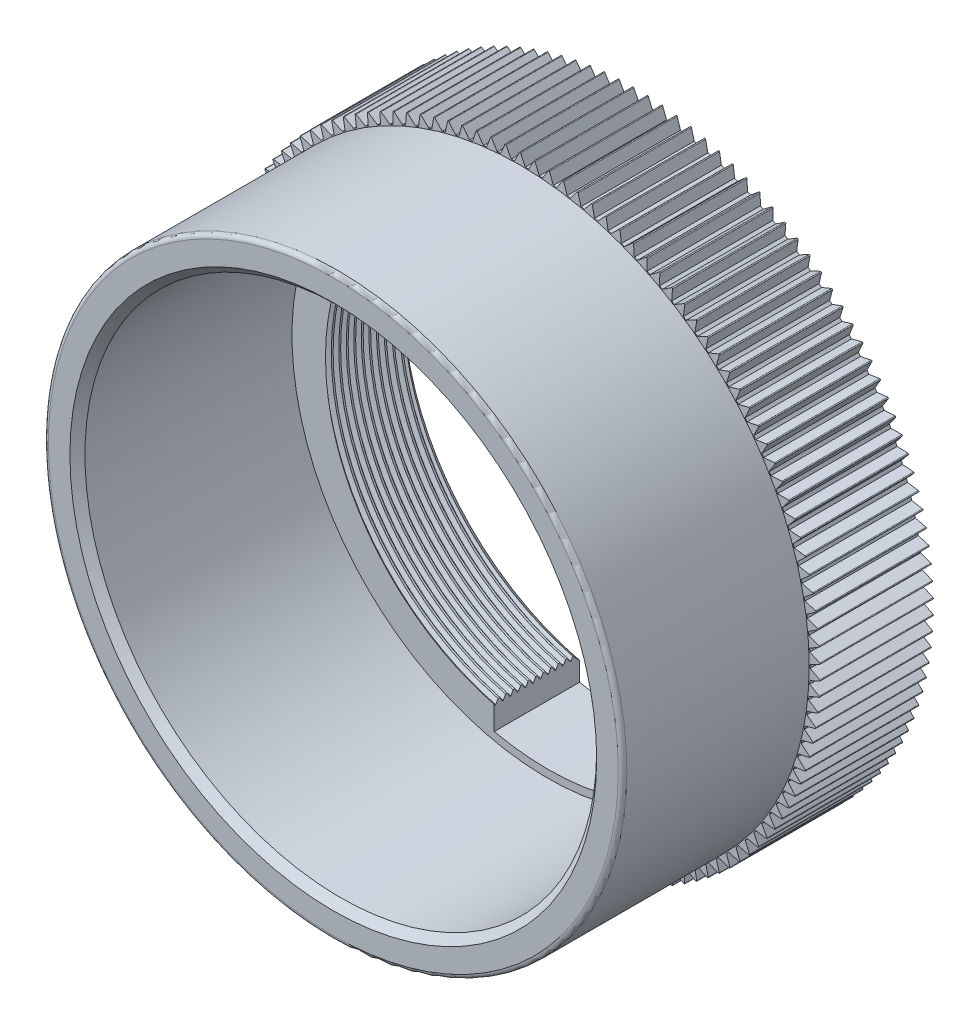
SolidWorks part; units mm, degrees
ref_plane "Plano frontal" through (0, 0, 0) normal (0, 0, 1) x (1, 0, 0)
ref_plane "Plano superior" through (0, 0, 0) normal (0, 1, 0) x (1, 0, 0)
ref_plane "Plano direito" through (0, 0, 0) normal (1, 0, 0) x (0, 0, -1)
sketch "Esboço1" plane through (0, 0, 0) normal (0, 0, 1) x (1, 0, 0)
  line L0 (0, 14) -> (0, 13.994) construction
  line L1 (0.4035, 13.5163) -> (0.6484, 13.9622)
  line L2 (-0.25, 13.52) -> (-0.027, 13.9772)
  line L3 (0.25, 13.52) -> (0.027, 13.9772)
  line L4 (0.9029, 13.4921) -> (0.7022, 13.9596)
  line L5 (1.056, 13.481) -> (1.3222, 13.9145)
  line L6 (1.5537, 13.4328) -> (1.3758, 13.9093)
  line L7 (1.7061, 13.4142) -> (1.9929, 13.8344)
  line L8 (2.2009, 13.342) -> (2.0462, 13.8266)
  line L9 (2.3522, 13.3162) -> (2.6589, 13.722)
  line L10 (2.8429, 13.2201) -> (2.7119, 13.7116)
  line L11 (2.9928, 13.187) -> (3.3188, 13.5775)
  line L12 (3.4783, 13.0673) -> (3.3711, 13.5646)
  line L13 (3.6264, 13.027) -> (3.9709, 13.4013)
  line L14 (4.1055, 12.884) -> (4.0226, 13.3859)
  line L15 (4.2516, 12.8366) -> (4.6137, 13.1938)
  line L16 (4.7232, 12.6706) -> (4.6646, 13.1759)
  line L17 (4.8668, 12.6162) -> (5.2458, 12.9555)
  line L18 (5.3299, 12.4276) -> (5.2957, 12.9352)
  line L19 (5.4706, 12.3663) -> (5.8656, 12.6869)
  line L20 (5.9241, 12.1556) -> (5.9145, 12.6642)
  line L21 (6.0617, 12.0875) -> (6.4717, 12.3887)
  line L22 (6.5044, 11.8552) -> (6.5194, 12.3637)
  line L23 (6.6386, 11.7806) -> (7.0626, 12.0616)
  line L24 (7.0696, 11.5271) -> (7.1091, 12.0342)
  line L25 (7.2, 11.4461) -> (7.6371, 11.7063)
  line L26 (7.6182, 11.1721) -> (7.6822, 11.6767)
  line L27 (7.7446, 11.0849) -> (8.1938, 11.3236)
  line L28 (8.1491, 10.791) -> (8.2374, 11.2919)
  line L29 (8.2711, 10.6977) -> (8.7313, 10.9145)
  line L30 (8.6609, 10.3847) -> (8.7733, 10.8808)
  line L31 (8.7783, 10.2856) -> (9.2484, 10.48)
  line L32 (9.1525, 9.9541) -> (9.2888, 10.4442)
  line L33 (9.265, 9.8495) -> (9.7439, 10.0209)
  line L34 (9.6228, 9.5003) -> (9.7825, 9.9832)
  line L35 (9.73, 9.3904) -> (10.2167, 9.5384)
  line L36 (10.0705, 9.0243) -> (10.2534, 9.4989)
  line L37 (10.1723, 8.9093) -> (10.6656, 9.0337)
  line L38 (10.4948, 8.5272) -> (10.7004, 8.9925)
  line L39 (10.5909, 8.4075) -> (11.0896, 8.5079)
  line L40 (10.8945, 8.0102) -> (11.1223, 8.465)
  line L41 (10.9847, 7.886) -> (11.4877, 7.9621)
  line L42 (11.2688, 7.4745) -> (11.5183, 7.9178)
  line L43 (11.3529, 7.3461) -> (11.859, 7.3978)
  line L44 (11.6167, 6.9213) -> (11.8874, 7.352)
  line L45 (11.6946, 6.789) -> (12.2025, 6.8162)
  line L46 (11.9375, 6.352) -> (12.2287, 6.7691)
  line L47 (12.0089, 6.2161) -> (12.5176, 6.2187)
  line L48 (12.2305, 5.7678) -> (12.5415, 6.1704)
  line L49 (12.2952, 5.6286) -> (12.8034, 5.6067)
  line L50 (12.4949, 5.1702) -> (12.8249, 5.5573)
  line L51 (12.5528, 5.028) -> (13.0593, 4.9816)
  line L52 (12.7301, 4.5605) -> (13.0785, 4.9312)
  line L53 (12.781, 4.4157) -> (13.2848, 4.3448)
  line L54 (12.9355, 3.9401) -> (13.3014, 4.2935)
  line L55 (12.9794, 3.793) -> (13.4792, 3.6979)
  line L56 (13.1108, 3.3106) -> (13.4933, 3.6459)
  line L57 (13.1475, 3.1615) -> (13.6421, 3.0424)
  line L58 (13.2554, 2.6733) -> (13.6537, 2.9897)
  line L59 (13.2849, 2.5226) -> (13.7731, 2.3797)
  line L60 (13.3691, 2.0298) -> (13.7822, 2.3266)
  line L61 (13.3913, 1.8778) -> (13.872, 1.7115)
  line L62 (13.4516, 1.3815) -> (13.8785, 1.658)
  line L63 (13.4664, 1.2287) -> (13.9385, 1.0393)
  line L64 (13.5026, 0.73) -> (13.9424, 0.9855)
  line L65 (13.51, 0.5766) -> (13.9725, 0.3647)
  line L66 (13.5221, 0.0768) -> (13.9738, 0.3108)
  line L67 (13.5221, -0.0768) -> (13.9738, -0.3108)
  line L68 (13.51, -0.5766) -> (13.9725, -0.3647)
  line L69 (13.5026, -0.73) -> (13.9424, -0.9855)
  line L70 (13.4664, -1.2287) -> (13.9385, -1.0393)
  line L71 (13.4516, -1.3815) -> (13.8785, -1.658)
  line L72 (13.3913, -1.8778) -> (13.872, -1.7115)
  line L73 (13.3691, -2.0298) -> (13.7822, -2.3266)
  line L74 (13.2849, -2.5226) -> (13.7731, -2.3797)
  line L75 (13.2554, -2.6733) -> (13.6537, -2.9897)
  line L76 (13.1475, -3.1615) -> (13.6421, -3.0424)
  line L77 (13.1108, -3.3106) -> (13.4933, -3.6459)
  line L78 (12.9794, -3.793) -> (13.4792, -3.6979)
  line L79 (12.9355, -3.9401) -> (13.3014, -4.2935)
  line L80 (12.781, -4.4157) -> (13.2848, -4.3448)
  line L81 (12.7301, -4.5605) -> (13.0785, -4.9312)
  line L82 (12.5528, -5.028) -> (13.0593, -4.9816)
  line L83 (12.4949, -5.1702) -> (12.8249, -5.5573)
  line L84 (12.2952, -5.6286) -> (12.8034, -5.6067)
  line L85 (12.2305, -5.7678) -> (12.5415, -6.1704)
  line L86 (12.0089, -6.2161) -> (12.5176, -6.2187)
  line L87 (11.9375, -6.352) -> (12.2287, -6.7691)
  line L88 (11.6946, -6.789) -> (12.2025, -6.8162)
  line L89 (11.6167, -6.9213) -> (11.8874, -7.352)
  line L90 (11.3529, -7.3461) -> (11.859, -7.3978)
  line L91 (11.2688, -7.4745) -> (11.5183, -7.9178)
  line L92 (10.9847, -7.886) -> (11.4877, -7.9621)
  line L93 (10.8945, -8.0102) -> (11.1223, -8.465)
  line L94 (10.5909, -8.4075) -> (11.0896, -8.5079)
  line L95 (10.4948, -8.5272) -> (10.7004, -8.9925)
  line L96 (10.1723, -8.9093) -> (10.6656, -9.0337)
  line L97 (10.0705, -9.0243) -> (10.2534, -9.4989)
  line L98 (9.73, -9.3904) -> (10.2167, -9.5384)
  line L99 (9.6228, -9.5003) -> (9.7825, -9.9832)
  line L100 (9.265, -9.8495) -> (9.7439, -10.0209)
  line L101 (9.1525, -9.9541) -> (9.2888, -10.4442)
  line L102 (8.7783, -10.2856) -> (9.2484, -10.48)
  line L103 (8.6609, -10.3847) -> (8.7733, -10.8808)
  line L104 (8.2711, -10.6977) -> (8.7313, -10.9145)
  line L105 (8.1491, -10.791) -> (8.2374, -11.2919)
  line L106 (7.7446, -11.0849) -> (8.1938, -11.3236)
  line L107 (7.6182, -11.1721) -> (7.6822, -11.6767)
  line L108 (7.2, -11.4461) -> (7.6371, -11.7063)
  line L109 (7.0696, -11.5271) -> (7.1091, -12.0342)
  line L110 (6.6386, -11.7806) -> (7.0626, -12.0616)
  line L111 (6.5044, -11.8552) -> (6.5194, -12.3637)
  line L112 (6.0617, -12.0875) -> (6.4717, -12.3887)
  line L113 (5.9241, -12.1556) -> (5.9145, -12.6642)
  line L114 (5.4706, -12.3663) -> (5.8656, -12.6869)
  line L115 (5.3299, -12.4276) -> (5.2957, -12.9352)
  line L116 (4.8668, -12.6162) -> (5.2458, -12.9555)
  line L117 (4.7232, -12.6706) -> (4.6646, -13.1759)
  line L118 (4.2516, -12.8366) -> (4.6137, -13.1938)
  line L119 (4.1055, -12.884) -> (4.0226, -13.3859)
  line L120 (3.6264, -13.027) -> (3.9709, -13.4013)
  line L121 (3.4783, -13.0673) -> (3.3711, -13.5646)
  line L122 (2.9928, -13.187) -> (3.3188, -13.5775)
  line L123 (2.8429, -13.2201) -> (2.7119, -13.7116)
  line L124 (2.3522, -13.3162) -> (2.6589, -13.722)
  line L125 (2.2009, -13.342) -> (2.0462, -13.8266)
  line L126 (1.7061, -13.4142) -> (1.9929, -13.8344)
  line L127 (1.5537, -13.4328) -> (1.3758, -13.9093)
  line L128 (1.056, -13.481) -> (1.3222, -13.9145)
  line L129 (0.9029, -13.4921) -> (0.7022, -13.9596)
  line L130 (0.4035, -13.5163) -> (0.6484, -13.9622)
  line L131 (0.25, -13.52) -> (0.027, -13.9772)
  line L132 (-0.25, -13.52) -> (-0.027, -13.9772)
  line L133 (-0.4035, -13.5163) -> (-0.6484, -13.9622)
  line L134 (-0.9029, -13.4921) -> (-0.7022, -13.9596)
  line L135 (-1.056, -13.481) -> (-1.3222, -13.9145)
  line L136 (-1.5537, -13.4328) -> (-1.3758, -13.9093)
  line L137 (-1.7061, -13.4142) -> (-1.9929, -13.8344)
  line L138 (-2.2009, -13.342) -> (-2.0462, -13.8266)
  line L139 (-2.3522, -13.3162) -> (-2.6589, -13.722)
  line L140 (-2.8429, -13.2201) -> (-2.7119, -13.7116)
  line L141 (-2.9928, -13.187) -> (-3.3188, -13.5775)
  line L142 (-3.4783, -13.0673) -> (-3.3711, -13.5646)
  line L143 (-3.6264, -13.027) -> (-3.9709, -13.4013)
  line L144 (-4.1055, -12.884) -> (-4.0226, -13.3859)
  line L145 (-4.2516, -12.8366) -> (-4.6137, -13.1938)
  line L146 (-4.7232, -12.6706) -> (-4.6646, -13.1759)
  line L147 (-4.8668, -12.6162) -> (-5.2458, -12.9555)
  line L148 (-5.3299, -12.4276) -> (-5.2957, -12.9352)
  line L149 (-5.4706, -12.3663) -> (-5.8656, -12.6869)
  line L150 (-5.9241, -12.1556) -> (-5.9145, -12.6642)
  line L151 (-6.0617, -12.0875) -> (-6.4717, -12.3887)
  line L152 (-6.5044, -11.8552) -> (-6.5194, -12.3637)
  line L153 (-6.6386, -11.7806) -> (-7.0626, -12.0616)
  line L154 (-7.0696, -11.5271) -> (-7.1091, -12.0342)
  line L155 (-7.2, -11.4461) -> (-7.6371, -11.7063)
  line L156 (-7.6182, -11.1721) -> (-7.6822, -11.6767)
  line L157 (-7.7446, -11.0849) -> (-8.1938, -11.3236)
  line L158 (-8.1491, -10.791) -> (-8.2374, -11.2919)
  line L159 (-8.2711, -10.6977) -> (-8.7313, -10.9145)
  line L160 (-8.6609, -10.3847) -> (-8.7733, -10.8808)
  line L161 (-8.7783, -10.2856) -> (-9.2484, -10.48)
  line L162 (-9.1525, -9.9541) -> (-9.2888, -10.4442)
  line L163 (-9.265, -9.8495) -> (-9.7439, -10.0209)
  line L164 (-9.6228, -9.5003) -> (-9.7825, -9.9832)
  line L165 (-9.73, -9.3904) -> (-10.2167, -9.5384)
  line L166 (-10.0705, -9.0243) -> (-10.2534, -9.4989)
  line L167 (-10.1723, -8.9093) -> (-10.6656, -9.0337)
  line L168 (-10.4948, -8.5272) -> (-10.7004, -8.9925)
  line L169 (-10.5909, -8.4075) -> (-11.0896, -8.5079)
  line L170 (-10.8945, -8.0102) -> (-11.1223, -8.465)
  line L171 (-10.9847, -7.886) -> (-11.4877, -7.9621)
  line L172 (-11.2688, -7.4745) -> (-11.5183, -7.9178)
  line L173 (-11.3529, -7.3461) -> (-11.859, -7.3978)
  line L174 (-11.6167, -6.9213) -> (-11.8874, -7.352)
  line L175 (-11.6946, -6.789) -> (-12.2025, -6.8162)
  line L176 (-11.9375, -6.352) -> (-12.2287, -6.7691)
  line L177 (-12.0089, -6.2161) -> (-12.5176, -6.2187)
  line L178 (-12.2305, -5.7678) -> (-12.5415, -6.1704)
  line L179 (-12.2952, -5.6286) -> (-12.8034, -5.6067)
  line L180 (-12.4949, -5.1702) -> (-12.8249, -5.5573)
  line L181 (-12.5528, -5.028) -> (-13.0593, -4.9816)
  line L182 (-12.7301, -4.5605) -> (-13.0785, -4.9312)
  line L183 (-12.781, -4.4157) -> (-13.2848, -4.3448)
  line L184 (-12.9355, -3.9401) -> (-13.3014, -4.2935)
  line L185 (-12.9794, -3.793) -> (-13.4792, -3.6979)
  line L186 (-13.1108, -3.3106) -> (-13.4933, -3.6459)
  line L187 (-13.1475, -3.1615) -> (-13.6421, -3.0424)
  line L188 (-13.2554, -2.6733) -> (-13.6537, -2.9897)
  line L189 (-13.2849, -2.5226) -> (-13.7731, -2.3797)
  line L190 (-13.3691, -2.0298) -> (-13.7822, -2.3266)
  line L191 (-13.3913, -1.8778) -> (-13.872, -1.7115)
  line L192 (-13.4516, -1.3815) -> (-13.8785, -1.658)
  line L193 (-13.4664, -1.2287) -> (-13.9385, -1.0393)
  line L194 (-13.5026, -0.73) -> (-13.9424, -0.9855)
  line L195 (-13.51, -0.5766) -> (-13.9725, -0.3647)
  line L196 (-13.5221, -0.0768) -> (-13.9738, -0.3108)
  line L197 (-13.5221, 0.0768) -> (-13.9738, 0.3108)
  line L198 (-13.51, 0.5766) -> (-13.9725, 0.3647)
  line L199 (-13.5026, 0.73) -> (-13.9424, 0.9855)
  line L200 (-13.4664, 1.2287) -> (-13.9385, 1.0393)
  line L201 (-13.4516, 1.3815) -> (-13.8785, 1.658)
  line L202 (-13.3913, 1.8778) -> (-13.872, 1.7115)
  line L203 (-13.3691, 2.0298) -> (-13.7822, 2.3266)
  line L204 (-13.2849, 2.5226) -> (-13.7731, 2.3797)
  line L205 (-13.2554, 2.6733) -> (-13.6537, 2.9897)
  line L206 (-13.1475, 3.1615) -> (-13.6421, 3.0424)
  line L207 (-13.1108, 3.3106) -> (-13.4933, 3.6459)
  line L208 (-12.9794, 3.793) -> (-13.4792, 3.6979)
  line L209 (-12.9355, 3.9401) -> (-13.3014, 4.2935)
  line L210 (-12.781, 4.4157) -> (-13.2848, 4.3448)
  line L211 (-12.7301, 4.5605) -> (-13.0785, 4.9312)
  line L212 (-12.5528, 5.028) -> (-13.0593, 4.9816)
  line L213 (-12.4949, 5.1702) -> (-12.8249, 5.5573)
  line L214 (-12.2952, 5.6286) -> (-12.8034, 5.6067)
  line L215 (-12.2305, 5.7678) -> (-12.5415, 6.1704)
  line L216 (-12.0089, 6.2161) -> (-12.5176, 6.2187)
  line L217 (-11.9375, 6.352) -> (-12.2287, 6.7691)
  line L218 (-11.6946, 6.789) -> (-12.2025, 6.8162)
  line L219 (-11.6167, 6.9213) -> (-11.8874, 7.352)
  line L220 (-11.3529, 7.3461) -> (-11.859, 7.3978)
  line L221 (-11.2688, 7.4745) -> (-11.5183, 7.9178)
  line L222 (-10.9847, 7.886) -> (-11.4877, 7.9621)
  line L223 (-10.8945, 8.0102) -> (-11.1223, 8.465)
  line L224 (-10.5909, 8.4075) -> (-11.0896, 8.5079)
  line L225 (-10.4948, 8.5272) -> (-10.7004, 8.9925)
  line L226 (-10.1723, 8.9093) -> (-10.6656, 9.0337)
  line L227 (-10.0705, 9.0243) -> (-10.2534, 9.4989)
  line L228 (-9.73, 9.3904) -> (-10.2167, 9.5384)
  line L229 (-9.6228, 9.5003) -> (-9.7825, 9.9832)
  line L230 (-9.265, 9.8495) -> (-9.7439, 10.0209)
  line L231 (-9.1525, 9.9541) -> (-9.2888, 10.4442)
  line L232 (-8.7783, 10.2856) -> (-9.2484, 10.48)
  line L233 (-8.6609, 10.3847) -> (-8.7733, 10.8808)
  line L234 (-8.2711, 10.6977) -> (-8.7313, 10.9145)
  line L235 (-8.1491, 10.791) -> (-8.2374, 11.2919)
  line L236 (-7.7446, 11.0849) -> (-8.1938, 11.3236)
  line L237 (-7.6182, 11.1721) -> (-7.6822, 11.6767)
  line L238 (-7.2, 11.4461) -> (-7.6371, 11.7063)
  line L239 (-7.0696, 11.5271) -> (-7.1091, 12.0342)
  line L240 (-6.6386, 11.7806) -> (-7.0626, 12.0616)
  line L241 (-6.5044, 11.8552) -> (-6.5194, 12.3637)
  line L242 (-6.0617, 12.0875) -> (-6.4717, 12.3887)
  line L243 (-5.9241, 12.1556) -> (-5.9145, 12.6642)
  line L244 (-5.4706, 12.3663) -> (-5.8656, 12.6869)
  line L245 (-5.3299, 12.4276) -> (-5.2957, 12.9352)
  line L246 (-4.8668, 12.6162) -> (-5.2458, 12.9555)
  line L247 (-4.7232, 12.6706) -> (-4.6646, 13.1759)
  line L248 (-4.2516, 12.8366) -> (-4.6137, 13.1938)
  line L249 (-4.1055, 12.884) -> (-4.0226, 13.3859)
  line L250 (-3.6264, 13.027) -> (-3.9709, 13.4013)
  line L251 (-3.4783, 13.0673) -> (-3.3711, 13.5646)
  line L252 (-2.9928, 13.187) -> (-3.3188, 13.5775)
  line L253 (-2.8429, 13.2201) -> (-2.7119, 13.7116)
  line L254 (-2.3522, 13.3162) -> (-2.6589, 13.722)
  line L255 (-2.2009, 13.342) -> (-2.0462, 13.8266)
  line L256 (-1.7061, 13.4142) -> (-1.9929, 13.8344)
  line L257 (-1.5537, 13.4328) -> (-1.3758, 13.9093)
  line L258 (-1.056, 13.481) -> (-1.3222, 13.9145)
  line L259 (-0.9029, 13.4921) -> (-0.7022, 13.9596)
  line L260 (-0.4035, 13.5163) -> (-0.6484, 13.9622)
  line L261 (0.25, 13.52) -> (0.4035, 13.5163)
  line L262 (0.9029, 13.4921) -> (1.056, 13.481)
  line L263 (1.5537, 13.4328) -> (1.7061, 13.4142)
  line L264 (2.2009, 13.342) -> (2.3522, 13.3162)
  line L265 (2.8429, 13.2201) -> (2.9928, 13.187)
  line L266 (3.4783, 13.0673) -> (3.6264, 13.027)
  line L267 (4.1055, 12.884) -> (4.2516, 12.8366)
  line L268 (4.7232, 12.6706) -> (4.8668, 12.6162)
  line L269 (5.3299, 12.4276) -> (5.4706, 12.3663)
  line L270 (5.9241, 12.1556) -> (6.0617, 12.0875)
  line L271 (6.5044, 11.8552) -> (6.6386, 11.7806)
  line L272 (7.0696, 11.5271) -> (7.2, 11.4461)
  line L273 (7.6182, 11.1721) -> (7.7446, 11.0849)
  line L274 (8.1491, 10.791) -> (8.2711, 10.6977)
  line L275 (8.6609, 10.3847) -> (8.7783, 10.2856)
  line L276 (9.1525, 9.9541) -> (9.265, 9.8495)
  line L277 (9.6228, 9.5003) -> (9.73, 9.3904)
  line L278 (10.0705, 9.0243) -> (10.1723, 8.9093)
  line L279 (10.4948, 8.5272) -> (10.5909, 8.4075)
  line L280 (10.8945, 8.0102) -> (10.9847, 7.886)
  line L281 (11.2688, 7.4745) -> (11.3529, 7.3461)
  line L282 (11.6167, 6.9213) -> (11.6946, 6.789)
  line L283 (11.9375, 6.352) -> (12.0089, 6.2161)
  line L284 (12.2305, 5.7678) -> (12.2952, 5.6286)
  line L285 (12.4949, 5.1702) -> (12.5528, 5.028)
  line L286 (12.7301, 4.5605) -> (12.781, 4.4157)
  line L287 (12.9355, 3.9401) -> (12.9794, 3.793)
  line L288 (13.1108, 3.3106) -> (13.1475, 3.1615)
  line L289 (13.2554, 2.6733) -> (13.2849, 2.5226)
  line L290 (13.3691, 2.0298) -> (13.3913, 1.8778)
  line L291 (13.4516, 1.3815) -> (13.4664, 1.2287)
  line L292 (13.5026, 0.73) -> (13.51, 0.5766)
  line L293 (13.5221, 0.0768) -> (13.5221, -0.0768)
  line L294 (13.51, -0.5766) -> (13.5026, -0.73)
  line L295 (13.4664, -1.2287) -> (13.4516, -1.3815)
  line L296 (13.3913, -1.8778) -> (13.3691, -2.0298)
  line L297 (13.2849, -2.5226) -> (13.2554, -2.6733)
  line L298 (13.1475, -3.1615) -> (13.1108, -3.3106)
  line L299 (12.9794, -3.793) -> (12.9355, -3.9401)
  line L300 (12.781, -4.4157) -> (12.7301, -4.5605)
  line L301 (12.5528, -5.028) -> (12.4949, -5.1702)
  line L302 (12.2952, -5.6286) -> (12.2305, -5.7678)
  line L303 (12.0089, -6.2161) -> (11.9375, -6.352)
  line L304 (11.6946, -6.789) -> (11.6167, -6.9213)
  line L305 (11.3529, -7.3461) -> (11.2688, -7.4745)
  line L306 (10.9847, -7.886) -> (10.8945, -8.0102)
  line L307 (10.5909, -8.4075) -> (10.4948, -8.5272)
  line L308 (10.1723, -8.9093) -> (10.0705, -9.0243)
  line L309 (9.73, -9.3904) -> (9.6228, -9.5003)
  line L310 (9.265, -9.8495) -> (9.1525, -9.9541)
  line L311 (8.7783, -10.2856) -> (8.6609, -10.3847)
  line L312 (8.2711, -10.6977) -> (8.1491, -10.791)
  line L313 (7.7446, -11.0849) -> (7.6182, -11.1721)
  line L314 (7.2, -11.4461) -> (7.0696, -11.5271)
  line L315 (6.6386, -11.7806) -> (6.5044, -11.8552)
  line L316 (6.0617, -12.0875) -> (5.9241, -12.1556)
  line L317 (5.4706, -12.3663) -> (5.3299, -12.4276)
  line L318 (4.8668, -12.6162) -> (4.7232, -12.6706)
  line L319 (4.2516, -12.8366) -> (4.1055, -12.884)
  line L320 (3.6264, -13.027) -> (3.4783, -13.0673)
  line L321 (2.9928, -13.187) -> (2.8429, -13.2201)
  line L322 (2.3522, -13.3162) -> (2.2009, -13.342)
  line L323 (1.7061, -13.4142) -> (1.5537, -13.4328)
  line L324 (1.056, -13.481) -> (0.9029, -13.4921)
  line L325 (0.4035, -13.5163) -> (0.25, -13.52)
  line L326 (-0.25, -13.52) -> (-0.4035, -13.5163)
  line L327 (-0.9029, -13.4921) -> (-1.056, -13.481)
  line L328 (-1.5537, -13.4328) -> (-1.7061, -13.4142)
  line L329 (-2.2009, -13.342) -> (-2.3522, -13.3162)
  line L330 (-2.8429, -13.2201) -> (-2.9928, -13.187)
  line L331 (-3.4783, -13.0673) -> (-3.6264, -13.027)
  line L332 (-4.1055, -12.884) -> (-4.2516, -12.8366)
  line L333 (-4.7232, -12.6706) -> (-4.8668, -12.6162)
  line L334 (-5.3299, -12.4276) -> (-5.4706, -12.3663)
  line L335 (-5.9241, -12.1556) -> (-6.0617, -12.0875)
  line L336 (-6.5044, -11.8552) -> (-6.6386, -11.7806)
  line L337 (-7.0696, -11.5271) -> (-7.2, -11.4461)
  line L338 (-7.6182, -11.1721) -> (-7.7446, -11.0849)
  line L339 (-8.1491, -10.791) -> (-8.2711, -10.6977)
  line L340 (-8.6609, -10.3847) -> (-8.7783, -10.2856)
  line L341 (-9.1525, -9.9541) -> (-9.265, -9.8495)
  line L342 (-9.6228, -9.5003) -> (-9.73, -9.3904)
  line L343 (-10.0705, -9.0243) -> (-10.1723, -8.9093)
  line L344 (-10.4948, -8.5272) -> (-10.5909, -8.4075)
  line L345 (-10.8945, -8.0102) -> (-10.9847, -7.886)
  line L346 (-11.2688, -7.4745) -> (-11.3529, -7.3461)
  line L347 (-11.6167, -6.9213) -> (-11.6946, -6.789)
  line L348 (-11.9375, -6.352) -> (-12.0089, -6.2161)
  line L349 (-12.2305, -5.7678) -> (-12.2952, -5.6286)
  line L350 (-12.4949, -5.1702) -> (-12.5528, -5.028)
  line L351 (-12.7301, -4.5605) -> (-12.781, -4.4157)
  line L352 (-12.9355, -3.9401) -> (-12.9794, -3.793)
  line L353 (-13.1108, -3.3106) -> (-13.1475, -3.1615)
  line L354 (-13.2554, -2.6733) -> (-13.2849, -2.5226)
  line L355 (-13.3691, -2.0298) -> (-13.3913, -1.8778)
  line L356 (-13.4516, -1.3815) -> (-13.4664, -1.2287)
  line L357 (-13.5026, -0.73) -> (-13.51, -0.5766)
  line L358 (-13.5221, -0.0768) -> (-13.5221, 0.0768)
  line L359 (-13.51, 0.5766) -> (-13.5026, 0.73)
  line L360 (-13.4664, 1.2287) -> (-13.4516, 1.3815)
  line L361 (-13.3913, 1.8778) -> (-13.3691, 2.0298)
  line L362 (-13.2849, 2.5226) -> (-13.2554, 2.6733)
  line L363 (-13.1475, 3.1615) -> (-13.1108, 3.3106)
  line L364 (-12.9794, 3.793) -> (-12.9355, 3.9401)
  line L365 (-12.781, 4.4157) -> (-12.7301, 4.5605)
  line L366 (-12.5528, 5.028) -> (-12.4949, 5.1702)
  line L367 (-12.2952, 5.6286) -> (-12.2305, 5.7678)
  line L368 (-12.0089, 6.2161) -> (-11.9375, 6.352)
  line L369 (-11.6946, 6.789) -> (-11.6167, 6.9213)
  line L370 (-11.3529, 7.3461) -> (-11.2688, 7.4745)
  line L371 (-10.9847, 7.886) -> (-10.8945, 8.0102)
  line L372 (-10.5909, 8.4075) -> (-10.4948, 8.5272)
  line L373 (-10.1723, 8.9093) -> (-10.0705, 9.0243)
  line L374 (-9.73, 9.3904) -> (-9.6228, 9.5003)
  line L375 (-9.265, 9.8495) -> (-9.1525, 9.9541)
  line L376 (-8.7783, 10.2856) -> (-8.6609, 10.3847)
  line L377 (-8.2711, 10.6977) -> (-8.1491, 10.791)
  line L378 (-7.7446, 11.0849) -> (-7.6182, 11.1721)
  line L379 (-7.2, 11.4461) -> (-7.0696, 11.5271)
  line L380 (-6.6386, 11.7806) -> (-6.5044, 11.8552)
  line L381 (-6.0617, 12.0875) -> (-5.9241, 12.1556)
  line L382 (-5.4706, 12.3663) -> (-5.3299, 12.4276)
  line L383 (-4.8668, 12.6162) -> (-4.7232, 12.6706)
  line L384 (-4.2516, 12.8366) -> (-4.1055, 12.884)
  line L385 (-3.6264, 13.027) -> (-3.4783, 13.0673)
  line L386 (-2.9928, 13.187) -> (-2.8429, 13.2201)
  line L387 (-2.3522, 13.3162) -> (-2.2009, 13.342)
  line L388 (-1.7061, 13.4142) -> (-1.5537, 13.4328)
  line L389 (-1.056, 13.481) -> (-0.9029, 13.4921)
  line L390 (-0.4035, 13.5163) -> (-0.25, 13.52)
  arc A0 (0.7022, 13.9596) -> (0.6484, 13.9622) centre (0.6746, 13.9477) ccw
  arc A1 (0.027, 13.9772) -> (-0.027, 13.9772) centre (0, 13.964) ccw
  arc A2 (1.3758, 13.9093) -> (1.3222, 13.9145) centre (1.3477, 13.8989) ccw
  arc A3 (2.0462, 13.8266) -> (1.9929, 13.8344) centre (2.0177, 13.8175) ccw
  arc A4 (2.7119, 13.7116) -> (2.6589, 13.722) centre (2.6829, 13.7039) ccw
  arc A5 (3.3711, 13.5646) -> (3.3188, 13.5775) centre (3.3418, 13.5583) ccw
  arc A6 (4.0226, 13.3859) -> (3.9709, 13.4013) centre (3.993, 13.381) ccw
  arc A7 (4.6646, 13.1759) -> (4.6137, 13.1938) centre (4.6348, 13.1724) ccw
  arc A8 (5.2957, 12.9352) -> (5.2458, 12.9555) centre (5.2658, 12.9331) ccw
  arc A9 (5.9145, 12.6642) -> (5.8656, 12.6869) centre (5.8845, 12.6636) ccw
  arc A10 (6.5194, 12.3637) -> (6.4717, 12.3887) centre (6.4894, 12.3645) ccw
  arc A11 (7.1091, 12.0342) -> (7.0626, 12.0616) centre (7.0792, 12.0366) ccw
  arc A12 (7.6822, 11.6767) -> (7.6371, 11.7063) centre (7.6525, 11.6805) ccw
  arc A13 (8.2374, 11.2919) -> (8.1938, 11.3236) centre (8.2079, 11.2971) ccw
  arc A14 (8.7733, 10.8808) -> (8.7313, 10.9145) centre (8.7441, 10.8874) ccw
  arc A15 (9.2888, 10.4442) -> (9.2484, 10.48) centre (9.2599, 10.4522) ccw
  arc A16 (9.7825, 9.9832) -> (9.7439, 10.0209) centre (9.754, 9.9927) ccw
  arc A17 (10.2534, 9.4989) -> (10.2167, 9.5384) centre (10.2254, 9.5097) ccw
  arc A18 (10.7004, 8.9925) -> (10.6656, 9.0337) centre (10.6729, 9.0046) ccw
  arc A19 (11.1223, 8.465) -> (11.0896, 8.5079) centre (11.0955, 8.4784) ccw
  arc A20 (11.5183, 7.9178) -> (11.4877, 7.9621) centre (11.4922, 7.9325) ccw
  arc A21 (11.8874, 7.352) -> (11.859, 7.3978) centre (11.862, 7.368) ccw
  arc A22 (12.2287, 6.7691) -> (12.2025, 6.8162) centre (12.2041, 6.7863) ccw
  arc A23 (12.5415, 6.1704) -> (12.5176, 6.2187) centre (12.5177, 6.1887) ccw
  arc A24 (12.8249, 5.5573) -> (12.8034, 5.6067) centre (12.8021, 5.5767) ccw
  arc A25 (13.0785, 4.9312) -> (13.0593, 4.9816) centre (13.0566, 4.9517) ccw
  arc A26 (13.3014, 4.2935) -> (13.2848, 4.3448) centre (13.2806, 4.3151) ccw
  arc A27 (13.4933, 3.6459) -> (13.4792, 3.6979) centre (13.4736, 3.6685) ccw
  arc A28 (13.6537, 2.9897) -> (13.6421, 3.0424) centre (13.6351, 3.0132) ccw
  arc A29 (13.7822, 2.3266) -> (13.7731, 2.3797) centre (13.7647, 2.3509) ccw
  arc A30 (13.8785, 1.658) -> (13.872, 1.7115) centre (13.8622, 1.6832) ccw
  arc A31 (13.9424, 0.9855) -> (13.9385, 1.0393) centre (13.9274, 1.0115) ccw
  arc A32 (13.9738, 0.3108) -> (13.9725, 0.3647) centre (13.96, 0.3374) ccw
  arc A33 (13.9725, -0.3647) -> (13.9738, -0.3108) centre (13.96, -0.3374) ccw
  arc A34 (13.9385, -1.0393) -> (13.9424, -0.9855) centre (13.9274, -1.0115) ccw
  arc A35 (13.872, -1.7115) -> (13.8785, -1.658) centre (13.8622, -1.6832) ccw
  arc A36 (13.7731, -2.3797) -> (13.7822, -2.3266) centre (13.7647, -2.3509) ccw
  arc A37 (13.6421, -3.0424) -> (13.6537, -2.9897) centre (13.6351, -3.0132) ccw
  arc A38 (13.4792, -3.6979) -> (13.4933, -3.6459) centre (13.4736, -3.6685) ccw
  arc A39 (13.2848, -4.3448) -> (13.3014, -4.2935) centre (13.2806, -4.3151) ccw
  arc A40 (13.0593, -4.9816) -> (13.0785, -4.9312) centre (13.0566, -4.9517) ccw
  arc A41 (12.8034, -5.6067) -> (12.8249, -5.5573) centre (12.8021, -5.5767) ccw
  arc A42 (12.5176, -6.2187) -> (12.5415, -6.1704) centre (12.5177, -6.1887) ccw
  arc A43 (12.2025, -6.8162) -> (12.2287, -6.7691) centre (12.2041, -6.7863) ccw
  arc A44 (11.859, -7.3978) -> (11.8874, -7.352) centre (11.862, -7.368) ccw
  arc A45 (11.4877, -7.9621) -> (11.5183, -7.9178) centre (11.4922, -7.9325) ccw
  arc A46 (11.0896, -8.5079) -> (11.1223, -8.465) centre (11.0955, -8.4784) ccw
  arc A47 (10.6656, -9.0337) -> (10.7004, -8.9925) centre (10.6729, -9.0046) ccw
  arc A48 (10.2167, -9.5384) -> (10.2534, -9.4989) centre (10.2254, -9.5097) ccw
  arc A49 (9.7439, -10.0209) -> (9.7825, -9.9832) centre (9.754, -9.9927) ccw
  arc A50 (9.2484, -10.48) -> (9.2888, -10.4442) centre (9.2599, -10.4522) ccw
  arc A51 (8.7313, -10.9145) -> (8.7733, -10.8808) centre (8.7441, -10.8874) ccw
  arc A52 (8.1938, -11.3236) -> (8.2374, -11.2919) centre (8.2079, -11.2971) ccw
  arc A53 (7.6371, -11.7063) -> (7.6822, -11.6767) centre (7.6525, -11.6805) ccw
  arc A54 (7.0626, -12.0616) -> (7.1091, -12.0342) centre (7.0792, -12.0366) ccw
  arc A55 (6.4717, -12.3887) -> (6.5194, -12.3637) centre (6.4894, -12.3645) ccw
  arc A56 (5.8656, -12.6869) -> (5.9145, -12.6642) centre (5.8845, -12.6636) ccw
  arc A57 (5.2458, -12.9555) -> (5.2957, -12.9352) centre (5.2658, -12.9331) ccw
  arc A58 (4.6137, -13.1938) -> (4.6646, -13.1759) centre (4.6348, -13.1724) ccw
  arc A59 (3.9709, -13.4013) -> (4.0226, -13.3859) centre (3.993, -13.381) ccw
  arc A60 (3.3188, -13.5775) -> (3.3711, -13.5646) centre (3.3418, -13.5583) ccw
  arc A61 (2.6589, -13.722) -> (2.7119, -13.7116) centre (2.6829, -13.7039) ccw
  arc A62 (1.9929, -13.8344) -> (2.0462, -13.8266) centre (2.0177, -13.8175) ccw
  arc A63 (1.3222, -13.9145) -> (1.3758, -13.9093) centre (1.3477, -13.8989) ccw
  arc A64 (0.6484, -13.9622) -> (0.7022, -13.9596) centre (0.6746, -13.9477) ccw
  arc A65 (-0.027, -13.9772) -> (0.027, -13.9772) centre (0, -13.964) ccw
  arc A66 (-0.7022, -13.9596) -> (-0.6484, -13.9622) centre (-0.6746, -13.9477) ccw
  arc A67 (-1.3758, -13.9093) -> (-1.3222, -13.9145) centre (-1.3477, -13.8989) ccw
  arc A68 (-2.0462, -13.8266) -> (-1.9929, -13.8344) centre (-2.0177, -13.8175) ccw
  arc A69 (-2.7119, -13.7116) -> (-2.6589, -13.722) centre (-2.6829, -13.7039) ccw
  arc A70 (-3.3711, -13.5646) -> (-3.3188, -13.5775) centre (-3.3418, -13.5583) ccw
  arc A71 (-4.0226, -13.3859) -> (-3.9709, -13.4013) centre (-3.993, -13.381) ccw
  arc A72 (-4.6646, -13.1759) -> (-4.6137, -13.1938) centre (-4.6348, -13.1724) ccw
  arc A73 (-5.2957, -12.9352) -> (-5.2458, -12.9555) centre (-5.2658, -12.9331) ccw
  arc A74 (-5.9145, -12.6642) -> (-5.8656, -12.6869) centre (-5.8845, -12.6636) ccw
  arc A75 (-6.5194, -12.3637) -> (-6.4717, -12.3887) centre (-6.4894, -12.3645) ccw
  arc A76 (-7.1091, -12.0342) -> (-7.0626, -12.0616) centre (-7.0792, -12.0366) ccw
  arc A77 (-7.6822, -11.6767) -> (-7.6371, -11.7063) centre (-7.6525, -11.6805) ccw
  arc A78 (-8.2374, -11.2919) -> (-8.1938, -11.3236) centre (-8.2079, -11.2971) ccw
  arc A79 (-8.7733, -10.8808) -> (-8.7313, -10.9145) centre (-8.7441, -10.8874) ccw
  arc A80 (-9.2888, -10.4442) -> (-9.2484, -10.48) centre (-9.2599, -10.4522) ccw
  arc A81 (-9.7825, -9.9832) -> (-9.7439, -10.0209) centre (-9.754, -9.9927) ccw
  arc A82 (-10.2534, -9.4989) -> (-10.2167, -9.5384) centre (-10.2254, -9.5097) ccw
  arc A83 (-10.7004, -8.9925) -> (-10.6656, -9.0337) centre (-10.6729, -9.0046) ccw
  arc A84 (-11.1223, -8.465) -> (-11.0896, -8.5079) centre (-11.0955, -8.4784) ccw
  arc A85 (-11.5183, -7.9178) -> (-11.4877, -7.9621) centre (-11.4922, -7.9325) ccw
  arc A86 (-11.8874, -7.352) -> (-11.859, -7.3978) centre (-11.862, -7.368) ccw
  arc A87 (-12.2287, -6.7691) -> (-12.2025, -6.8162) centre (-12.2041, -6.7863) ccw
  arc A88 (-12.5415, -6.1704) -> (-12.5176, -6.2187) centre (-12.5177, -6.1887) ccw
  arc A89 (-12.8249, -5.5573) -> (-12.8034, -5.6067) centre (-12.8021, -5.5767) ccw
  arc A90 (-13.0785, -4.9312) -> (-13.0593, -4.9816) centre (-13.0566, -4.9517) ccw
  arc A91 (-13.3014, -4.2935) -> (-13.2848, -4.3448) centre (-13.2806, -4.3151) ccw
  arc A92 (-13.4933, -3.6459) -> (-13.4792, -3.6979) centre (-13.4736, -3.6685) ccw
  arc A93 (-13.6537, -2.9897) -> (-13.6421, -3.0424) centre (-13.6351, -3.0132) ccw
  arc A94 (-13.7822, -2.3266) -> (-13.7731, -2.3797) centre (-13.7647, -2.3509) ccw
  arc A95 (-13.8785, -1.658) -> (-13.872, -1.7115) centre (-13.8622, -1.6832) ccw
  arc A96 (-13.9424, -0.9855) -> (-13.9385, -1.0393) centre (-13.9274, -1.0115) ccw
  arc A97 (-13.9738, -0.3108) -> (-13.9725, -0.3647) centre (-13.96, -0.3374) ccw
  arc A98 (-13.9725, 0.3647) -> (-13.9738, 0.3108) centre (-13.96, 0.3374) ccw
  arc A99 (-13.9385, 1.0393) -> (-13.9424, 0.9855) centre (-13.9274, 1.0115) ccw
  arc A100 (-13.872, 1.7115) -> (-13.8785, 1.658) centre (-13.8622, 1.6832) ccw
  arc A101 (-13.7731, 2.3797) -> (-13.7822, 2.3266) centre (-13.7647, 2.3509) ccw
  arc A102 (-13.6421, 3.0424) -> (-13.6537, 2.9897) centre (-13.6351, 3.0132) ccw
  arc A103 (-13.4792, 3.6979) -> (-13.4933, 3.6459) centre (-13.4736, 3.6685) ccw
  arc A104 (-13.2848, 4.3448) -> (-13.3014, 4.2935) centre (-13.2806, 4.3151) ccw
  arc A105 (-13.0593, 4.9816) -> (-13.0785, 4.9312) centre (-13.0566, 4.9517) ccw
  arc A106 (-12.8034, 5.6067) -> (-12.8249, 5.5573) centre (-12.8021, 5.5767) ccw
  arc A107 (-12.5176, 6.2187) -> (-12.5415, 6.1704) centre (-12.5177, 6.1887) ccw
  arc A108 (-12.2025, 6.8162) -> (-12.2287, 6.7691) centre (-12.2041, 6.7863) ccw
  arc A109 (-11.859, 7.3978) -> (-11.8874, 7.352) centre (-11.862, 7.368) ccw
  arc A110 (-11.4877, 7.9621) -> (-11.5183, 7.9178) centre (-11.4922, 7.9325) ccw
  arc A111 (-11.0896, 8.5079) -> (-11.1223, 8.465) centre (-11.0955, 8.4784) ccw
  arc A112 (-10.6656, 9.0337) -> (-10.7004, 8.9925) centre (-10.6729, 9.0046) ccw
  arc A113 (-10.2167, 9.5384) -> (-10.2534, 9.4989) centre (-10.2254, 9.5097) ccw
  arc A114 (-9.7439, 10.0209) -> (-9.7825, 9.9832) centre (-9.754, 9.9927) ccw
  arc A115 (-9.2484, 10.48) -> (-9.2888, 10.4442) centre (-9.2599, 10.4522) ccw
  arc A116 (-8.7313, 10.9145) -> (-8.7733, 10.8808) centre (-8.7441, 10.8874) ccw
  arc A117 (-8.1938, 11.3236) -> (-8.2374, 11.2919) centre (-8.2079, 11.2971) ccw
  arc A118 (-7.6371, 11.7063) -> (-7.6822, 11.6767) centre (-7.6525, 11.6805) ccw
  arc A119 (-7.0626, 12.0616) -> (-7.1091, 12.0342) centre (-7.0792, 12.0366) ccw
  arc A120 (-6.4717, 12.3887) -> (-6.5194, 12.3637) centre (-6.4894, 12.3645) ccw
  arc A121 (-5.8656, 12.6869) -> (-5.9145, 12.6642) centre (-5.8845, 12.6636) ccw
  arc A122 (-5.2458, 12.9555) -> (-5.2957, 12.9352) centre (-5.2658, 12.9331) ccw
  arc A123 (-4.6137, 13.1938) -> (-4.6646, 13.1759) centre (-4.6348, 13.1724) ccw
  arc A124 (-3.9709, 13.4013) -> (-4.0226, 13.3859) centre (-3.993, 13.381) ccw
  arc A125 (-3.3188, 13.5775) -> (-3.3711, 13.5646) centre (-3.3418, 13.5583) ccw
  arc A126 (-2.6589, 13.722) -> (-2.7119, 13.7116) centre (-2.6829, 13.7039) ccw
  arc A127 (-1.9929, 13.8344) -> (-2.0462, 13.8266) centre (-2.0177, 13.8175) ccw
  arc A128 (-1.3222, 13.9145) -> (-1.3758, 13.9093) centre (-1.3477, 13.8989) ccw
  arc A129 (-0.6484, 13.9622) -> (-0.7022, 13.9596) centre (-0.6746, 13.9477) ccw
  point P8 (0, 13.52)
  point P657 (0, 0)
  point P916 (0, 0)
  dimension "D1" = 130
  dimension "D4" = 0.03
  dimension "D2" = 130
  dimension "D3" = 0.5
extrude "Ressalto-extrusão1" add sketch "Esboço1" along normal blind 5.28
sketch "Esboço2" plane through (0, 0, 5.28) normal (0, 0, 1) x (1, 0, 0)
  circle A0 centre (0, 0) radius 13.48
  dimension "D1" = 26.96
extrude "Ressalto-extrusão2" add sketch "Esboço2" along normal blind 8.7
sketch "Esboço3" plane through (0, 0, 13.98) normal (0, 0, 1) x (1, 0, 0)
  circle A0 centre (0, 0) radius 11.925
  dimension "D1" = 23.85
extrude "Corte-extrusão1" cut sketch "Esboço3" against normal blind 10
sketch "Esboço4" plane through (0, 0, 3.98) normal (0, 0, 1) x (1, 0, 0)
  circle A0 centre (0, 0) radius 10.35
  dimension "D1" = 20.7
extrude "Corte-extrusão2" cut sketch "Esboço4" against normal blind 26
chamfer "Chanfro1" distance 0.35 angle 45 1 edges at (10.35, 0, 0)
thread "Rosca1" pitch 0.35 method cut profile "Perfil da rosca1" start angle 0, offset 1, length 0, pitch 0.35, diameter 20.7
ref_plane "Plano1" through (10.35, 0, -0.65) normal (0, -1, 0) x (1, 0, 0)
sketch "Perfil da rosca1" plane through (10.35, 0, -0.65) normal (0, -1, 0) x (1, 0, 0)
  line L0 (0, 0) -> (0, 0.35) construction
  line L1 (0, 0) -> (0.1894, 0.1094)
  line L2 (0.1894, 0.1094) -> (0.1894, 0.1531)
  line L3 (0.1894, 0.1531) -> (0, 0.2625)
  line L4 (0.1894, 0.1312) -> (0, 0.1312) construction
  line L11 (0, 0) -> (0, 0.2625)
  point P2 (0, 0)
  dimension "Pitch" = 0.35
  dimension "Profile_Angle" = 60
  dimension "Profile_Land" = 0.0437
  dimension "Profile_Height" = 0.1894
chamfer "Chanfro2" distance 0.35 angle 45 1 edges at (11.925, 0, 13.98)
fillet "Filete1" radius 0.2 1 edges at (13.48, 0, 13.98)
sketch "Esboço8" plane through (0, 0, 0) normal (0, 0, -1) x (-1, 0, 0)
  line L2 (-2.5, -11.2864) -> (-2.5, 11.2864)
  line L4 (2.5, -11.2864) -> (2.5, 11.2864)
  arc A0 (2.5, 11.2864) -> (-2.5, 11.2864) centre (0, 0) ccw
  arc A1 (-2.5, -11.2864) -> (2.5, -11.2864) centre (0, 0) ccw
  dimension "D1" = 23.12
extrude "Corte-extrusão3" cut sketch "Esboço8" against normal blind 26
